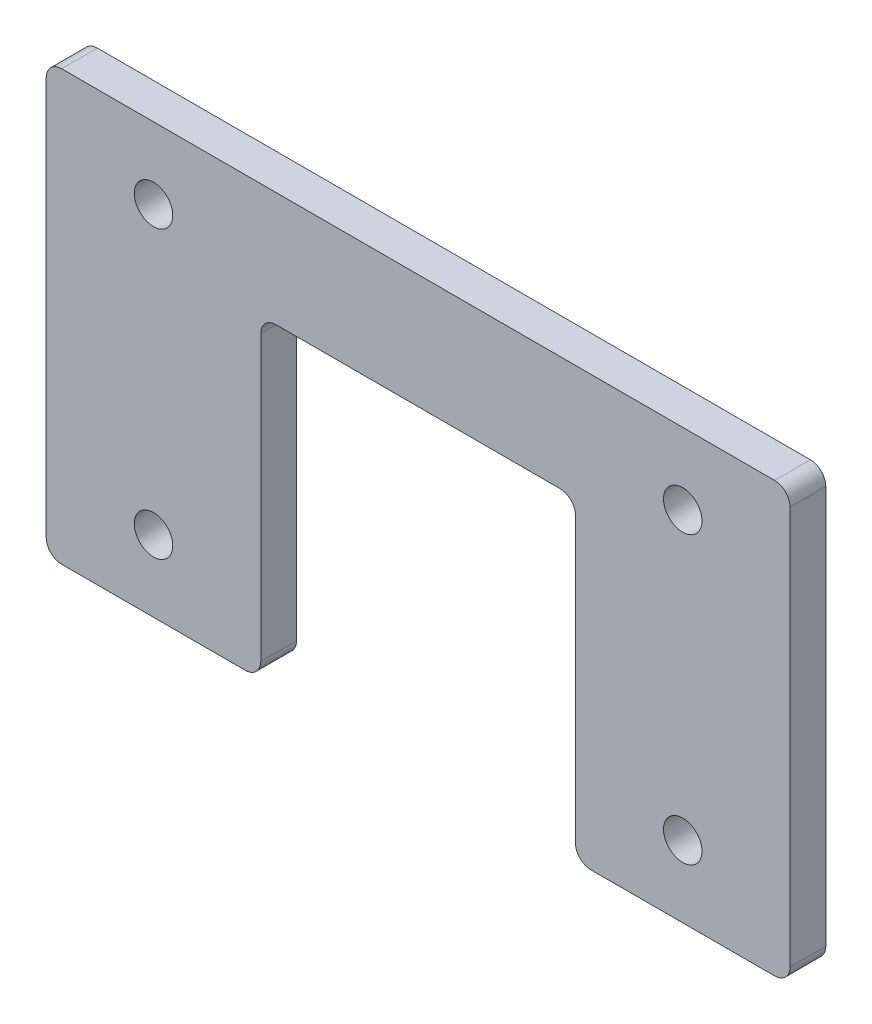
SolidWorks part; units mm, degrees
ref_plane "Front Plane" through (0, 0, 0) normal (0, 0, 1) x (1, 0, 0)
ref_plane "Top Plane" through (0, 0, 0) normal (0, 1, 0) x (1, 0, 0)
ref_plane "Right Plane" through (0, 0, 0) normal (1, 0, 0) x (0, 0, -1)
ref_plane "Plane1" through (0, 0, 0) normal (0, 0, 1) x (1, 0, 0)
sketch "Sketch1" plane through (0, 0, 0) normal (0, 0, 1) x (1, 0, 0)
  line L0 (326.2186, 421.8223) -> (351.9097, 421.8223)
  line L1 (354.0642, 423.9768) -> (354.0642, 463.6679)
  line L2 (356.2186, 465.8223) -> (395.9097, 465.8223)
  line L3 (398.0642, 463.6679) -> (398.0642, 423.9768)
  line L4 (400.2187, 421.8223) -> (425.9097, 421.8223)
  line L5 (428.0642, 423.9768) -> (428.0642, 479.6679)
  line L6 (425.9097, 481.8223) -> (326.2186, 481.8223)
  line L7 (324.0642, 479.6679) -> (324.0642, 423.9768)
  circle A0 centre (339.0642, 471.8223) radius 2.6931
  circle A1 centre (339.0642, 431.8223) radius 2.6931
  circle A2 centre (413.0642, 431.8223) radius 2.6931
  circle A3 centre (413.0642, 471.8223) radius 2.6931
  arc A4 (324.0642, 423.9768) -> (326.2186, 421.8223) centre (326.2186, 423.9768) ccw
  arc A5 (351.9097, 421.8223) -> (354.0642, 423.9768) centre (351.9097, 423.9768) ccw
  arc A6 (354.0642, 463.6679) -> (356.2186, 465.8223) centre (356.2186, 463.6679) cw
  arc A7 (395.9097, 465.8223) -> (398.0642, 463.6679) centre (395.9097, 463.6679) cw
  arc A8 (398.0642, 423.9768) -> (400.2187, 421.8223) centre (400.2187, 423.9768) ccw
  arc A9 (425.9097, 421.8223) -> (428.0642, 423.9768) centre (425.9097, 423.9768) ccw
  arc A10 (428.0642, 479.6679) -> (425.9097, 481.8223) centre (425.9097, 479.6679) ccw
  arc A11 (326.2186, 481.8223) -> (324.0642, 479.6679) centre (326.2186, 479.6679) ccw
  point P34 (339.0642, 421.8223)
  point P37 (413.0642, 421.8223)
  dimension "D1" = 30
  dimension "D2" = 30
  dimension "D3" = 104
  dimension "D4" = 60
  dimension "D5" = 10
  dimension "D6" = 15
  dimension "D7" = 10
  dimension "D8" = 44
extrude "Boss-Extrude1" add sketch "Sketch1" against normal blind 5
sketch "Sketch3" plane through (0, 0, 0) normal (0, 0, 1) x (1, 0, 0)
  line L0 (376.0642, 481.8223) -> (376.0642, 421.6199) construction
  line L1 (425.9097, 481.8223) -> (326.2186, 481.8223) construction
ref_axis "Axis1" through (376.0642, 481.8223, 0) along (0, -1, 0)
ref_plane "Plane2" through (376.0642, 0, 0) normal (-1, 0, 0) x (0, -1, 0)
